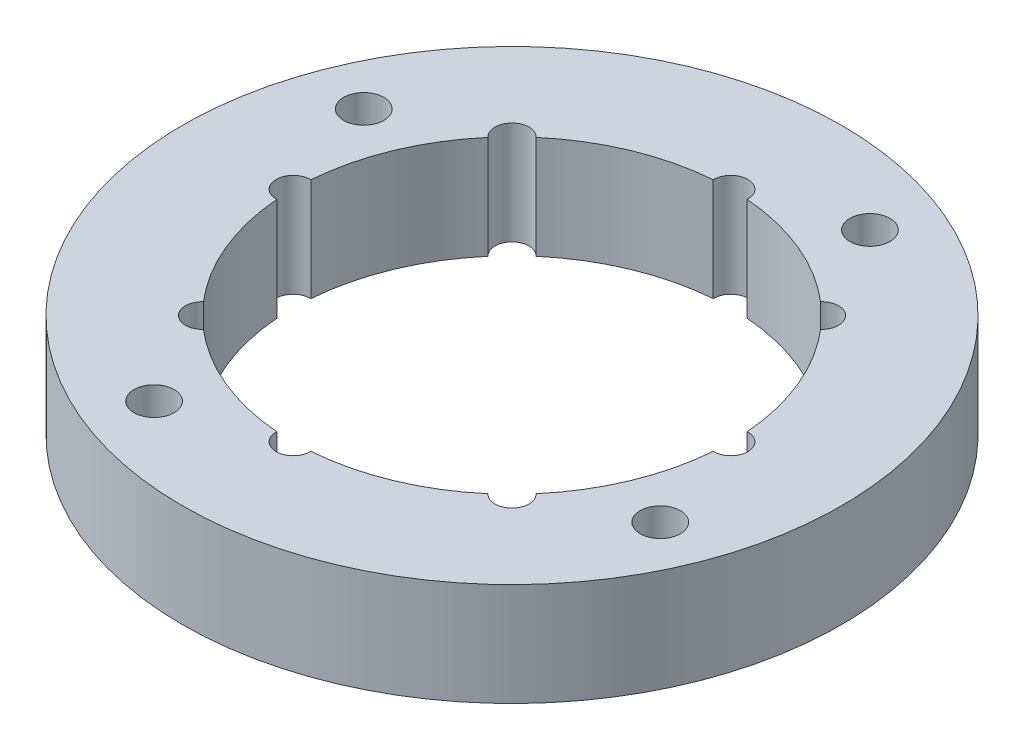
SolidWorks part; units mm, degrees
ref_plane "Front Plane" through (0, 0, 0) normal (0, 0, 1) x (1, 0, 0)
ref_plane "Top Plane" through (0, 0, 0) normal (0, 1, 0) x (1, 0, 0)
ref_plane "Right Plane" through (0, 0, 0) normal (1, 0, 0) x (0, 0, -1)
sketch "1.5in Socket" plane through (0, 0, 0) normal (0, 1, 0) x (1, 0, 0)
  line L0 (0, 0) -> (-19.083, 19.083) construction
  line L1 (0, 26.9875) -> (0, 0)
  line L2 (19.083, 19.083) -> (0, 0) construction
  line L3 (26.9875, 0) -> (0, 0)
  line L4 (19.083, -19.083) -> (0, 0) construction
  line L5 (0, -26.9875) -> (0, 0)
  line L6 (-19.083, -19.083) -> (0, 0) construction
  line L7 (-26.9875, 0) -> (0, 0) construction
  line L8 (-12.9278, -31.2105) -> (0, 0) construction
  line L9 (-31.2105, 12.9278) -> (0, 0) construction
  line L10 (31.2105, -12.9278) -> (0, 0) construction
  line L11 (12.9278, 31.2105) -> (0, 0) construction
  circle A0 centre (0, 0) radius 40.64
  arc A1 (-2.0939, 26.9061) -> (2.0939, 26.9061) centre (0, 26.9875) cw
  arc A2 (2.0939, 26.9061) -> (17.5449, 20.5061) centre (0, 0) cw
  arc A3 (17.5449, 20.5061) -> (20.5061, 17.5449) centre (19.083, 19.083) cw
  arc A4 (20.5061, 17.5449) -> (26.9061, 2.0939) centre (0, 0) cw
  arc A5 (26.9061, 2.0939) -> (26.9061, -2.0939) centre (26.9875, 0) cw
  arc A6 (26.9061, -2.0939) -> (20.5061, -17.5449) centre (0, 0) cw
  arc A7 (20.5061, -17.5449) -> (17.5449, -20.5061) centre (19.083, -19.083) cw
  arc A8 (17.5449, -20.5061) -> (2.0939, -26.9061) centre (0, 0) cw
  arc A9 (2.0939, -26.9061) -> (-2.0939, -26.9061) centre (0, -26.9875) cw
  arc A10 (-2.0939, -26.9061) -> (-17.5449, -20.5061) centre (0, 0) cw
  arc A11 (-17.5449, -20.5061) -> (-20.5061, -17.5449) centre (-19.083, -19.083) cw
  arc A12 (-20.5061, -17.5449) -> (-26.9061, -2.0939) centre (0, 0) cw
  arc A13 (-26.9061, -2.0939) -> (-26.9061, 2.0939) centre (-26.9875, 0) cw
  arc A14 (-26.9061, 2.0939) -> (-20.5061, 17.5449) centre (0, 0) cw
  arc A15 (-20.5061, 17.5449) -> (-17.5449, 20.5061) centre (-19.083, 19.083) cw
  arc A16 (-17.5449, 20.5061) -> (-2.0939, 26.9061) centre (0, 0) cw
  arc A18 (-2.0939, 26.9061) -> (-17.5449, 20.5061) centre (0, 0) ccw
  arc A19 (-17.5449, 20.5061) -> (-20.5061, 17.5449) centre (-19.083, 19.083) ccw
  arc A20 (-20.5061, 17.5449) -> (-26.9061, 2.0939) centre (0, 0) ccw
  arc A21 (-26.9061, 2.0939) -> (-26.9061, -2.0939) centre (-26.9875, 0) ccw
  arc A22 (-26.9061, -2.0939) -> (-20.5061, -17.5449) centre (0, 0) ccw
  arc A23 (-20.5061, -17.5449) -> (-17.5449, -20.5061) centre (-19.083, -19.083) ccw
  arc A24 (-17.5449, -20.5061) -> (-2.0939, -26.9061) centre (0, 0) ccw
  arc A25 (-2.0939, -26.9061) -> (2.0939, -26.9061) centre (0, -26.9875) ccw
  arc A26 (2.0939, -26.9061) -> (17.5449, -20.5061) centre (0, 0) ccw
  arc A27 (17.5449, -20.5061) -> (20.5061, -17.5449) centre (19.083, -19.083) ccw
  arc A28 (20.5061, -17.5449) -> (26.9061, -2.0939) centre (0, 0) ccw
  arc A29 (26.9061, -2.0939) -> (26.9061, 2.0939) centre (26.9875, 0) ccw
  arc A30 (26.9061, 2.0939) -> (20.5061, 17.5449) centre (0, 0) ccw
  arc A31 (20.5061, 17.5449) -> (17.5449, 20.5061) centre (19.083, 19.083) ccw
  arc A32 (17.5449, 20.5061) -> (2.0939, 26.9061) centre (0, 0) ccw
  arc A33 (2.0939, 26.9061) -> (-2.0939, 26.9061) centre (0, 26.9875) ccw
  circle A34 centre (-12.9278, -31.2105) radius 2.475
  circle A35 centre (-31.2105, 12.9278) radius 2.475
  circle A36 centre (31.2105, -12.9278) radius 2.475
  circle A37 centre (12.9278, 31.2105) radius 2.475
  point P27 (-19.083, -19.083)
  point P28 (-26.9875, 0)
  point P29 (0, 0)
  point P30 (0, -26.9875)
  point P31 (19.083, -19.083)
  point P32 (26.9875, 0)
  point P33 (19.083, 19.083)
  point P34 (0, 26.9875)
  point P35 (-19.083, 19.083)
  point P36 (0, 0)
  dimension "D1" = 2.0955
  dimension "D2" = 2.0955
  dimension "D3" = 2.0955
  dimension "D4" = 2.0955
  dimension "D5" = 2.0955
  dimension "D6" = 2.0955
  dimension "D7" = 2.0955
  dimension "D8" = 2.0955
  dimension "D9" = 26.9875
  dimension "D10" = 26.9875
  dimension "D11" = 26.9875
  dimension "D12" = 26.9875
  dimension "D13" = 26.9875
  dimension "D14" = 26.9875
  dimension "D15" = 26.9875
  dimension "D16" = 26.9875
  dimension "D17" = 81.28
  dimension "D26" = 4.95
  dimension "D28" = 33.782
  dimension "D30" = 4.95
  dimension "D31" = 4.95
  dimension "D32" = 4.95
  dimension "D18" = 26.9875
  dimension "D19" = 26.9875
  dimension "D20" = 26.9875
  dimension "D21" = 26.9875
  dimension "D22" = 26.9875
  dimension "D23" = 26.9875
  dimension "D24" = 26.9875
  dimension "D25" = 26.9875
  dimension "D27" = 33.782
  dimension "D29" = 90
  dimension "D33" = 90
  dimension "D34" = 90
  dimension "D35" = 33.782
  dimension "D36" = 33.782
  dimension "D37" = 67.5
extrude "Boss-Extrude1" add sketch "1.5in Socket" along normal blind 12.7 contours A0 A37 A36 A35 A34 A15 A16 A1 A2 A3 A4 A5 A6 A7 A8 A9 A10 A11 A12 A13 A14 region at (-39.4905, 0, 0)
